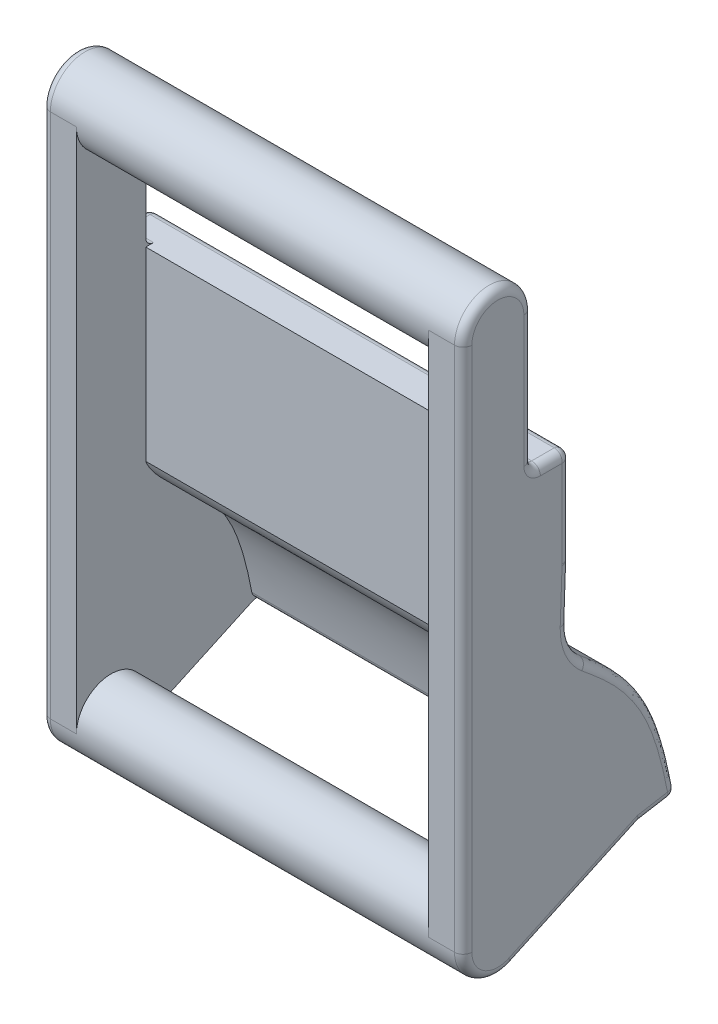
SolidWorks part; units mm, degrees
ref_plane "Plan de face" through (0, 0, 0) normal (0, 0, 1) x (1, 0, 0)
ref_plane "Plan de dessus" through (0, 0, 0) normal (0, 1, 0) x (1, 0, 0)
ref_plane "Plan de droite" through (0, 0, 0) normal (1, 0, 0) x (0, 0, -1)
sketch "Esquisse1" plane through (0, 0, 0) normal (1, 0, 0) x (0, 0, -1)
  line L0 (0, 0) -> (0, -30.31) construction
  line L1 (2, 0) -> (2, -30.31)
  line L2 (-2, 0) -> (-2, -30.31)
  arc A2 (2, 0) -> (-2, 0) centre (0, 0) ccw
  arc A3 (-2, -30.31) -> (2, -30.31) centre (0, -30.31) ccw
  point P3 (0, -15.155)
  dimension "D1" = 30.31
  dimension "D2" = 2
extrude "Boss.-Extru.1" add sketch "Esquisse1" along normal blind 2
sketch "Esquisse2" plane through (2, 0, 0) normal (1, 0, 0) x (0, 0, -1)
  circle A0 centre (0, 0) radius 2
  circle A1 centre (0, -30.31) radius 2
  dimension "D1" = 4
  dimension "D2" = 4
extrude "Boss.-Extru.2" add sketch "Esquisse2" along normal blind 20.3
pattern_linear "Répétition linéaire1" count 2 spacing 22.3 along (1, 0, 0) of "Boss.-Extru.1"
sketch "Esquisse3" plane through (24.3, 0, 0) normal (1, 0, 0) x (0, 0, -1)
  line L1 (4.2, -13.5842) -> (4.2, -8)
  line L5 (2, -18.6992) -> (2, -8)
  line L9 (-2.9999, 0.0234) -> (-1.5501, -28.6671) construction
  line L10 (-5.1999, -0.0323) -> (-3.7136, -29.4455) construction
  line L12 (2, -8) -> (4.2, -8)
  line L14 (0, 0) -> (0, -27.1685) construction
  line L15 (2, -27.9739) -> (2, 2.2361) construction
  line L16 (4.2, -28.3241) -> (4.2, 3.0659) construction
  line L17 (0, -13.5842) -> (12.2828, -13.5842) construction
  line L18 (2, -30.31) -> (2, 0) construction
  line L19 (8.1941, -28.7349) -> (10.3622, -28.362)
  line L20 (4.2, -13.5842) -> (4.049, -17.8983)
  arc A7 (-1.5501, -28.6671) -> (2, -27.9739) centre (0, -27.1685) ccw construction
  arc A8 (-3.7136, -29.4455) -> (4.2, -28.3241) centre (0, -27.1685) ccw construction
  arc A9 (2, 2.2361) -> (-2.9999, 0.0234) centre (0, 0) ccw construction
  arc A10 (4.2, 3.0659) -> (-5.1999, -0.0323) centre (0, 0) ccw construction
  spline S0 degree 3 poles (2, -18.6992) (2.4173, -19.7668) (4.9325, -21.5055) (7.3716, -24.3686) (8.0409, -27.8449) (8.1941, -28.7349) knots 0 0 0 0 0.321086 0.652681 1 1 1 1
  spline S1 degree 1 poles (4.049, -17.8983) (10.3622, -28.362) knots 0 0 1 1 construction
  spline S2 degree 3 poles (4.049, -17.8983) (4.0551, -17.9137) (4.0627, -17.9304) (4.143, -18.0647) (4.3588, -18.3268) (4.7997, -18.7443) (5.5577, -19.3794) (6.7138, -20.3434) (7.9459, -21.6989) (8.8051, -23.0755) (9.3417, -24.3329) (9.6567, -25.2709) (9.9099, -26.1836) (10.1091, -27.0357) (10.235, -27.6589) (10.3154, -28.0935) (10.3462, -28.2689) (10.3622, -28.362) knots 0 0 0 0 0.03125 0.0625 0.125 0.1875 0.25 0.375 0.5 0.625 0.6875 0.75 0.8125 0.875 0.9375 0.96875 1 1 1 1
  dimension "D1" = 8
  dimension "D2" = 2.2
  dimension "D4" = 2.2
extrude "Boss.-Extru.3" add sketch "Esquisse3" against normal up to surface (24.3 mm away) up to face at (0, -15.155, 0)
sketch "Esquisse4" plane through (0, 0, 0) normal (-1, 0, 0) x (0, 0, 1)
  line L0 (-2, -18.6992) -> (-2, -30.31)
  line L1 (-8.1941, -28.7349) -> (-0.8373, -32.1263)
  arc A0 (-2, -30.31) -> (2, -30.31) centre (0, -30.31) ccw construction
  arc A1 (-2, -30.31) -> (2, -30.31) centre (0, -30.31) ccw
  spline S0 degree 3 poles (-14.0559, 971.2409) (5.23, -88.2775) (-14.6714, -32.9374) (2.1586, -13.1817) (38.3109, -6.8558) (-967.0274, 243.4097) knots -2.992889 -2.992889 -2.992889 -2.992889 0.347319 0.678914 3.907326 3.907326 3.907326 3.907326 only from (-8.1941, -28.7349) to (-2, -18.6992) construction
  spline S1 degree 3 poles (-8.1941, -28.7349) (-8.0409, -27.8449) (-7.3716, -24.3686) (-4.9325, -21.5055) (-2.4173, -19.7668) (-2, -18.6992) knots 0 0 0 0 0.347319 0.678914 1 1 1 1
  spline M9 degree 3 poles (-2, -18.6992) (-2.4173, -19.7668) (-4.9325, -21.5055) (-7.3716, -24.3686) (-8.0409, -27.8449) (-8.1941, -28.7349) knots 0 0 0 0 0.321086 0.652681 1 1 1 1
  line M10 (-2, -18.6992) -> (-2, -30.31)
  arc M11 (-2, -30.31) -> (2, -30.31) centre (0, -30.31) ccw
extrude "Boss.-Extru.4" add sketch "Esquisse4" against normal up to surface (2 mm away) contours L1 M9 M11 M10 region at (0, -25.9884, -4.3666) up to face at (2, -14.5532, -0.6667)
sketch "Esquisse5" plane through (24.3, 0, 0) normal (1, 0, 0) x (0, 0, -1)
  line L0 (2, -30.31) -> (2, -18.6992) construction
  line L1 (2, -30.31) -> (2, -18.6992)
  line L2 (8.1941, -28.7349) -> (0.8373, -32.1263)
  arc A0 (0.8373, -32.1263) -> (-2, -30.31) centre (0, -30.31) ccw construction
  arc A1 (0.8373, -32.1263) -> (2, -30.31) centre (0, -30.31) ccw
  spline S0 degree 3 poles (14.0559, 971.2409) (-5.23, -88.2775) (14.6714, -32.9374) (-2.1586, -13.1817) (-38.3109, -6.8558) (967.0274, 243.4097) knots -2.992889 -2.992889 -2.992889 -2.992889 0.347319 0.678914 3.907326 3.907326 3.907326 3.907326 only from (8.1941, -28.7349) to (2, -18.6992) construction
  spline S1 degree 3 poles (8.1941, -28.7349) (8.0409, -27.8449) (7.3716, -24.3686) (4.9325, -21.5055) (2.4173, -19.7668) (2, -18.6992) knots 0 0 0 0 0.347319 0.678914 1 1 1 1
extrude "Boss.-Extru.5" add sketch "Esquisse5" against normal up to surface (2 mm away) up to face at (22.3, -14.5532, -0.6667)
fillet "Congé3" radius 0.45 5 edges at (1, -8, -2) (12.15, -8, -4.2) (23.3, -8, -2) (12.15, -28.7349, -8.1941) (12.15, -28.362, -10.3622)
fillet "Congé6" radius 3 2 edges at (12.15, -13.5842, -4.2) (12.15, -17.8983, -4.049)
fillet "Congé5" radius 0.5 27 edges at (0, -28.2524, -10.2087) (0, -28.5869, -9.0549) (0, -31.9944, 1.0783) (0, -15.155, 2) (0, 2, 0) (0, -3.775, -2) (0, -7.8682, -2.1318) (0, -8, -3.1) (0, -8.1318, -4.0682) (24.3, -28.2524, -10.2087) (24.3, -28.5869, -9.0549) (24.3, 2, 0) (24.3, -3.775, -2) (24.3, -7.8682, -2.1318) (24.3, -8, -3.1) (24.3, -8.1318, -4.0682) (0, -10.9909, -4.2) (24.3, -10.9909, -4.2) (0, -17.9666, -4.3489) (0, -15.1408, -4.1455) (0, -13.5842, -4.1995) (24.3, -13.5842, -4.1995) (24.3, -15.1408, -4.1455) (24.3, -17.9666, -4.3489) (0, -30.4306, -4.5157)
